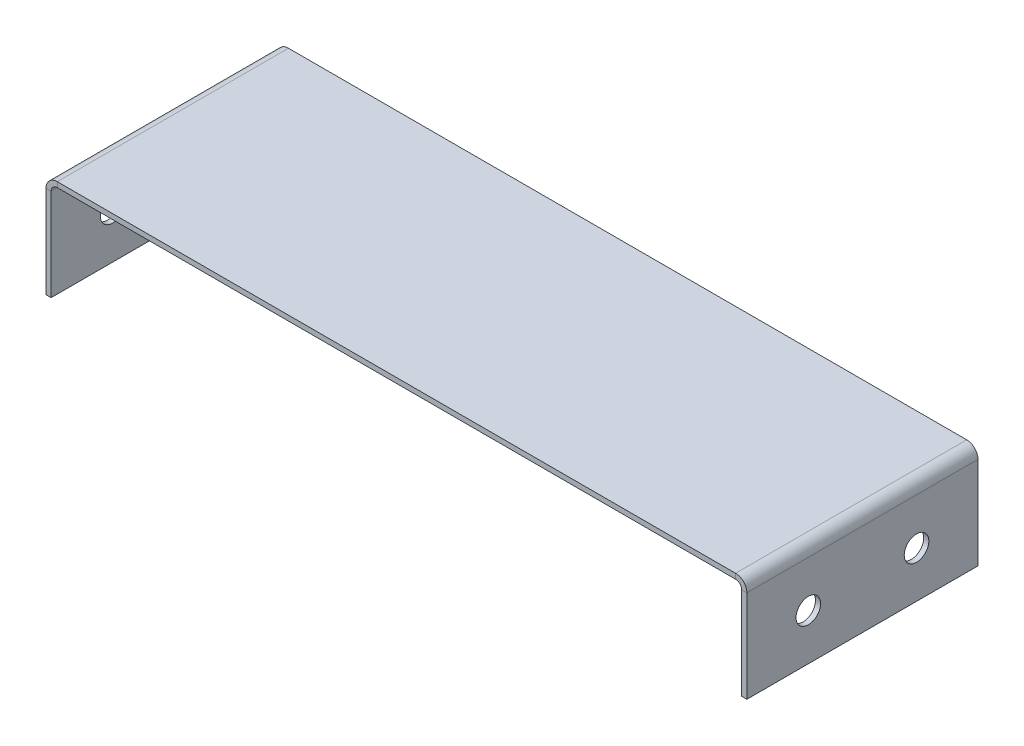
SolidWorks part; units mm, degrees
note: The reader was unsure of these and kept them because the rebuilt part matched: flange length of "Edge-Flange1", "Edge-Flange2".
ref_plane "Front Plane" through (0, 0, 0) normal (0, 0, 1) x (1, 0, 0)
ref_plane "Top Plane" through (0, 0, 0) normal (0, 1, 0) x (1, 0, 0)
ref_plane "Right Plane" through (0, 0, 0) normal (1, 0, 0) x (0, 0, -1)
sketch "Sketch1" plane through (0, 0, 0) normal (0, 1, 0) x (1, 0, 0)
  line L1 (0, 0) -> (361.95, 0)
  line L2 (0, 0) -> (0, 119.38)
  line L3 (0, 119.38) -> (361.95, 119.38)
  line L4 (361.95, 0) -> (361.95, 119.38)
  dimension "D1" = 361.95
  dimension "D2" = 119.38
base flange "Base-Flange1" sketch "Sketch1" thickness 2.6568 reverse thickness direction no parameters "D1"=3.175
edge flange "Edge-Flange1" sketch "Sketch8" flange angle 90 flange length 50.8 flange position material inside bend radius 3.175 thickness 2.6568 relief rectangular parameters "D6"=10
sketch "Sketch8" plane through (0, -2.6568, 0) normal (-1, 0, 0) x (0, 0, -1)
  line L0 (119.38, 0) -> (0, 0) construction
  line L1 (119.38, 0) -> (0, 0)
  line L2 (0, 0) -> (0, 50.8)
  line L3 (0, 50.8) -> (119.38, 50.8)
  line L4 (119.38, 50.8) -> (119.38, 0)
bend "EdgeBend1" bend radius 3.175 bend angle 90 parameters "D5"=1
edge flange "Edge-Flange2" sketch "Sketch11" flange angle 90 flange length 50.8 flange position material inside bend radius 3.175 thickness 2.6568 relief rectangular parameters "D6"=10
sketch "Sketch11" plane through (361.95, -2.6568, 0) normal (1, 0, 0) x (0, 0, 1)
  line L0 (0, 0) -> (-119.38, 0) construction
  line L1 (0, 0) -> (-119.38, 0)
  line L2 (-119.38, 0) -> (-119.38, 50.8)
  line L3 (-119.38, 50.8) -> (0, 50.8)
  line L4 (0, 50.8) -> (0, 0)
bend "EdgeBend2" bend radius 3.175 bend angle 90 parameters "D5"=2
sketch "Sketch12" plane through (0, 0, 0) normal (-1, 0, 0) x (0, 0, 1)
  line L0 (-119.38, -29.6443) -> (0, -29.6443) construction
  line L1 (-119.38, -5.8318) -> (-119.38, -53.4568) construction
  line L2 (0, -53.4568) -> (0, -5.8318) construction
  circle A0 centre (-87.63, -29.6443) radius 6.35
  circle A1 centre (-31.75, -29.6443) radius 6.35
  dimension "D1" = 12.7
  dimension "D2" = 12.7
  dimension "D3" = 31.75
  dimension "D4" = 31.75
extrude "Cut-Extrude1" cut sketch "Sketch12" against normal through all normal cut yes
sketch "Bend-Lines1" [suppressed] plane through (0, 0, 0) normal (0, 1, 0) x (1, 0, 0)
sketch "Bounding-Box1" [suppressed] plane through (0, 0, 0) normal (0, 1, 0) x (1, 0, 0)
sheet metal parameters "Sheet-Metal1" thickness 2.6568 parameters "D1"=3.175
flat pattern "Flat-Pattern1" [suppressed]
sketch "Bend-Lines2" plane through (0, 0, 0) normal (0, 1, 0) x (1, 0, 0)
sketch3d "Bounding-Box2" [suppressed]
  line L0 (-355.6, 119.38, 0) -> (0, 119.38, 0) construction
  line L1 (-355.6, 0, 0) -> (0, 0, 0) construction
  line L2 (-355.6, 119.38, 0) -> (-355.6, 0, 0) construction
  line L3 (0, 119.38, 0) -> (0, 0, 0) construction
sheet metal parameters "Sheet-Metal2" thickness 2.6568 parameters "D1"=3.175
flat pattern "Flat-Pattern1"
sketch "Bend-Lines2" plane through (0, 0, 0) normal (0, 1, 0) x (1, 0, 0)
  line L0 (2.2949, 119.38) -> (2.2949, 0) construction
  line L1 (2.2949, 119.38) -> (2.2949, 0) construction
sketch3d "Bounding-Box2" [suppressed]
  line L0 (355.6, 119.38, 0) -> (-48.8671, 119.38, 0) construction
  line L1 (355.6, 0, 0) -> (-48.8671, 0, 0) construction
  line L2 (355.6, 119.38, 0) -> (355.6, 0, 0) construction
  line L3 (-48.8671, 119.38, 0) -> (-48.8671, 0, 0) construction
bend of the flat pattern "Flatten-<EdgeBend1>1"
sheet metal parameters "Sheet-Metal3" thickness 2.6568 parameters "D1"=3.175
flat pattern "Flat-Pattern1"
sketch "Bend-Lines2" plane through (0, 0, 0) normal (0, 1, 0) x (1, 0, 0)
  line L0 (2.2949, 119.38) -> (2.2949, 0) construction
  line L1 (2.2949, 119.38) -> (2.2949, 0) construction
  line L2 (359.6551, 0) -> (359.6551, 119.38) construction
  line L3 (359.6551, 0) -> (359.6551, 119.38) construction
sketch3d "Bounding-Box2" [suppressed]
  line L0 (410.8171, 119.38, 0) -> (-48.8671, 119.38, 0) construction
  line L1 (410.8171, 0, 0) -> (-48.8671, 0, 0) construction
  line L2 (410.8171, 119.38, 0) -> (410.8171, 0, 0) construction
  line L3 (-48.8671, 119.38, 0) -> (-48.8671, 0, 0) construction
bend of the flat pattern "Flatten-<EdgeBend1>1"
bend of the flat pattern "Flatten-<EdgeBend2>1"
sheet metal parameters "Sheet-Metal4" thickness 2.6568 parameters "D1"=3.175
flat pattern "Flat-Pattern1"
sketch "Bend-Lines2" plane through (0, 0, 0) normal (0, 1, 0) x (1, 0, 0)
  line L0 (2.2949, 119.38) -> (2.2949, 0) construction
  line L1 (2.2949, 119.38) -> (2.2949, 0) construction
  line L2 (359.6551, 0) -> (359.6551, 119.38) construction
  line L3 (359.6551, 0) -> (359.6551, 119.38) construction
sketch3d "Bounding-Box2" [suppressed]
  line L0 (410.8171, 119.38, 0) -> (-48.8671, 119.38, 0) construction
  line L1 (410.8171, 0, 0) -> (-48.8671, 0, 0) construction
  line L2 (410.8171, 119.38, 0) -> (410.8171, 0, 0) construction
  line L3 (-48.8671, 119.38, 0) -> (-48.8671, 0, 0) construction
bend of the flat pattern "Flatten-<EdgeBend1>1"
bend of the flat pattern "Flatten-<EdgeBend2>1"
